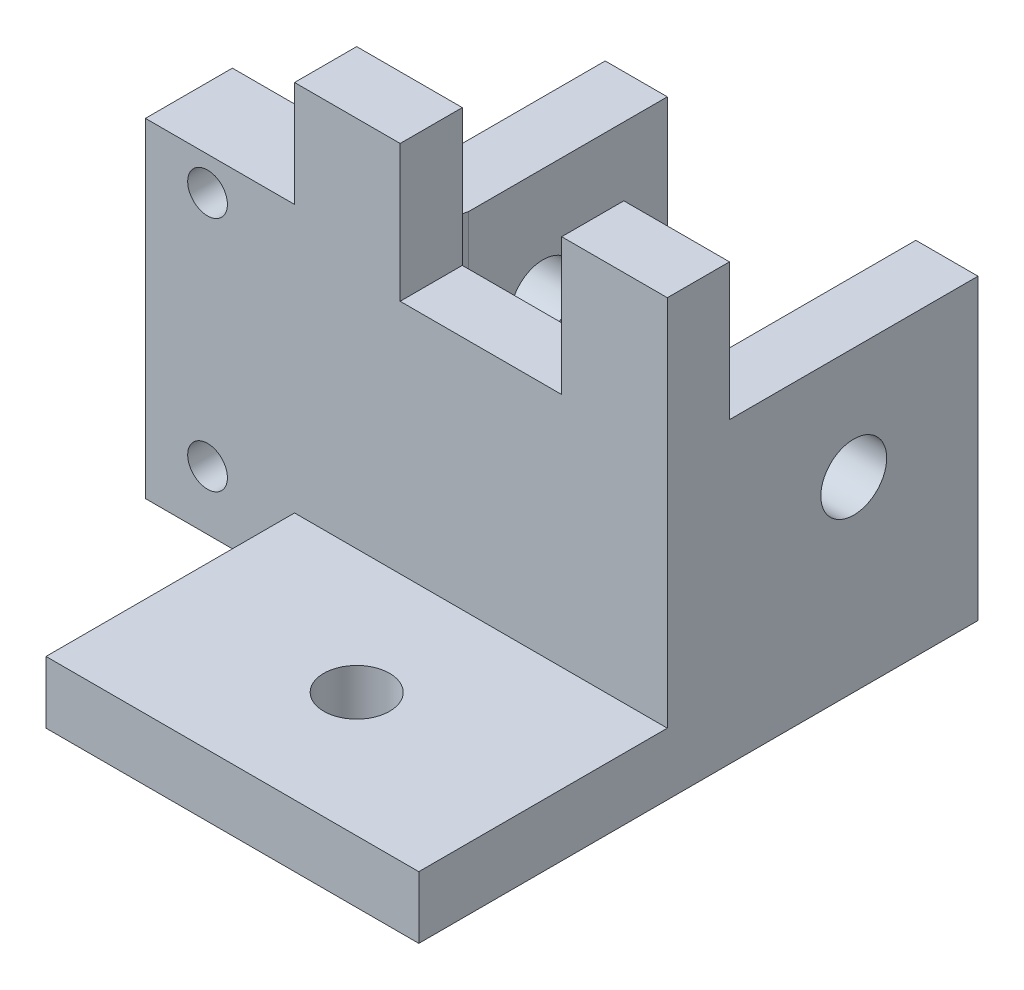
SolidWorks part; units mm, degrees
ref_plane "Front Plane" through (0, 0, 0) normal (0, 0, 1) x (1, 0, 0)
ref_plane "Top Plane" through (0, 0, 0) normal (0, 1, 0) x (1, 0, 0)
ref_plane "Right Plane" through (0, 0, 0) normal (1, 0, 0) x (0, 0, -1)
sketch "Sketch1" plane through (0, 0, 0) normal (0, 1, 0) x (1, 0, 0)
  line L1 (0, 0) -> (30, 0)
  line L2 (0, 0) -> (0, 45)
  line L3 (0, 45) -> (30, 45)
  line L4 (30, 0) -> (30, 45)
  dimension "D1" = 30
  dimension "D2" = 45
extrude "Boss-Extrude1" add sketch "Sketch1" along normal blind 5
sketch "Sketch2" plane through (0, 5, 0) normal (0, 1, 0) x (1, 0, 0)
  line L11 (0, 45) -> (0, 0) construction
  line L12 (0, 25) -> (30, 25)
  line L13 (0, 25) -> (0, 20)
  line L14 (0, 20) -> (30, 20)
  line L15 (30, 25) -> (30, 20)
  line L16 (30, 0) -> (30, 45) construction
  line L17 (30, 45) -> (0, 45) construction
  dimension "D1" = 5
  dimension "D2" = 20
extrude "Boss-Extrude2" add sketch "Sketch2" along normal blind 30
sketch "Sketch3" plane through (0, 5, 0) normal (0, 1, 0) x (1, 0, 0)
  line L1 (0, 25) -> (5, 25)
  line L2 (0, 25) -> (0, 45)
  line L3 (0, 45) -> (5, 45)
  line L4 (5, 25) -> (5, 45)
  line L5 (30, 45) -> (0, 45) construction
  line L6 (0, 45) -> (0, 25) construction
  line L7 (25, 45) -> (30, 45)
  line L8 (25, 45) -> (25, 25)
  line L9 (25, 25) -> (30, 25)
  line L10 (30, 45) -> (30, 25)
  line L11 (0, 25) -> (30, 25) construction
  dimension "D1" = 5
  dimension "D2" = 5
  dimension "D3" = 20
  dimension "D4" = 0
extrude "Boss-Extrude3" add sketch "Sketch3" along normal blind 19
sketch "Sketch4" plane through (0, 35, 0) normal (0, 1, 0) x (1, 0, 0)
  line L0 (0, 20) -> (30, 20) construction
  line L1 (8.5, 20) -> (21.5, 20)
  line L2 (8.5, 20) -> (8.5, 25)
  line L3 (8.5, 25) -> (21.5, 25)
  line L4 (21.5, 20) -> (21.5, 25)
  line L5 (0, 25) -> (30, 25) construction
  line L6 (0, 25) -> (0, 20) construction
  dimension "D1" = 13
  dimension "D2" = 8.5
extrude "Cut-Extrude1" cut sketch "Sketch4" against normal blind 11
sketch "Sketch5" plane through (0, 0, 0) normal (0, -1, 0) x (1, 0, 0)
  line L0 (0, 0) -> (30, 0) construction
  line L1 (30, 0) -> (30, -45) construction
  line L2 (30, -45) -> (0, -45) construction
  circle A0 centre (15, -10) radius 2.65
  circle A1 centre (15, -35) radius 2.65
  dimension "D1" = 5.3
  dimension "D4" = 5.3
  dimension "D2" = 10
  dimension "D3" = 15
  dimension "D5" = 10
  dimension "D6" = 15
extrude "Cut-Extrude2" cut sketch "Sketch5" against normal blind 10
sketch "Sketch6" plane through (30, 0, 0) normal (1, 0, 0) x (0, 0, -1)
  line L0 (45, 24) -> (45, 0) construction
  line L1 (0, 0) -> (45, 0) construction
  circle A0 centre (35, 15) radius 2.65
  dimension "D1" = 5.3
  dimension "D2" = 10
  dimension "D3" = 15
extrude "Cut-Extrude3" cut sketch "Sketch6" against normal through all both and the other way through all
sketch "Sketch7" plane through (0, 0, -45) normal (0, 0, -1) x (-1, 0, 0)
  line L0 (-25, 5) -> (-26, 5)
  line L1 (-26, 5) -> (-25, 9)
  line L2 (-25, 24) -> (-25, 5) construction
  line L3 (-25, 9) -> (-25, 5)
  line L4 (-5, 5) -> (-4, 5)
  line L5 (-4, 5) -> (-5, 9)
  line L6 (-5, 24) -> (-5, 5) construction
  line L7 (-5, 9) -> (-5, 5)
  dimension "D1" = 4
  dimension "D2" = 4
  dimension "D3" = 1
  dimension "D4" = 1
extrude "Cut-Extrude4" cut sketch "Sketch7" against normal up to surface (20 mm away) up to face at (15, 24.5, -25)
sketch "Sketch8" plane through (0, 24, 0) normal (0, 1, 0) x (1, 0, 0)
  line L0 (25, 25) -> (26, 25)
  line L1 (25, 25) -> (30, 25) construction
  line L2 (26, 25) -> (25, 29)
  line L3 (25, 45) -> (25, 25) construction
  line L4 (25, 29) -> (25, 25)
  line L5 (5, 25) -> (5, 29)
  line L6 (5, 25) -> (5, 45) construction
  line L7 (5, 29) -> (4, 25)
  line L8 (8.5, 25) -> (0, 25) construction
  line L9 (4, 25) -> (5, 25)
  dimension "D1" = 1
  dimension "D2" = 4
  dimension "D3" = 1
  dimension "D4" = 4
extrude "Cut-Extrude5" cut sketch "Sketch8" against normal up to surface (19 mm away) up to face at (15, 5, -12.65)
sketch "Sketch9" plane through (0, 0, 0) normal (-1, 0, 0) x (0, 0, 1)
  line L0 (-45, 0) -> (0, 0) construction
  line L1 (-25, 26.5) -> (-20, 26.5)
  line L2 (-25, 26.5) -> (-25, 0)
  line L3 (-25, 0) -> (-20, 0)
  line L4 (-20, 26.5) -> (-20, 0)
  line L5 (-20, 35) -> (-20, 5) construction
  line L7 (-25, 35) -> (-25, 24) construction
  point P9 (-25, 24)
  point P10 (-25, 27.2552)
  dimension "D1" = 26.5
extrude "Boss-Extrude4" add sketch "Sketch9" along normal blind 12
sketch "Sketch10" plane through (0, 0, -25) normal (0, 0, -1) x (-1, 0, 0)
  line L0 (12, 26.5) -> (12, 0) construction
  line L1 (12, 0) -> (0, 0)
  line L2 (12, 0) -> (12, 9)
  line L3 (12, 9) -> (0, 9)
  line L4 (0, 0) -> (0, 9)
  line L5 (12, 0) -> (0, 0) construction
  line L6 (0, 24) -> (0, 0) construction
  line L7 (12, 26.5) -> (0, 26.5)
  line L8 (12, 26.5) -> (12, 19.5)
  line L9 (12, 19.5) -> (0, 19.5)
  line L10 (0, 26.5) -> (0, 19.5)
  line L11 (12, 26.5) -> (0, 26.5) construction
  dimension "D1" = 9
  dimension "D2" = 7
extrude "Boss-Extrude5" add sketch "Sketch10" along normal blind 2
chamfer "Chamfer1" distance 2 angle 45 1 edges at (-6, 19.5, -27)
chamfer "Chamfer2" distance 2 angle 45 1 edges at (-6, 9, -27)
sketch "Sketch11" plane through (0, 0, -27) normal (0, 0, -1) x (-1, 0, 0)
  line L0 (12, 26.5) -> (0, 26.5) construction
  line L1 (12, 21.5) -> (12, 26.5) construction
  circle A0 centre (7, 23.8) radius 1.6
  circle A1 centre (7, 4.75) radius 1.6
  point P8 (0, 0)
  dimension "D1" = 3.2
  dimension "D2" = 3.2
  dimension "D3" = 19.05
  dimension "D4" = 2.7
  dimension "D5" = 5
extrude "Cut-Extrude6" cut sketch "Sketch11" against normal through all
